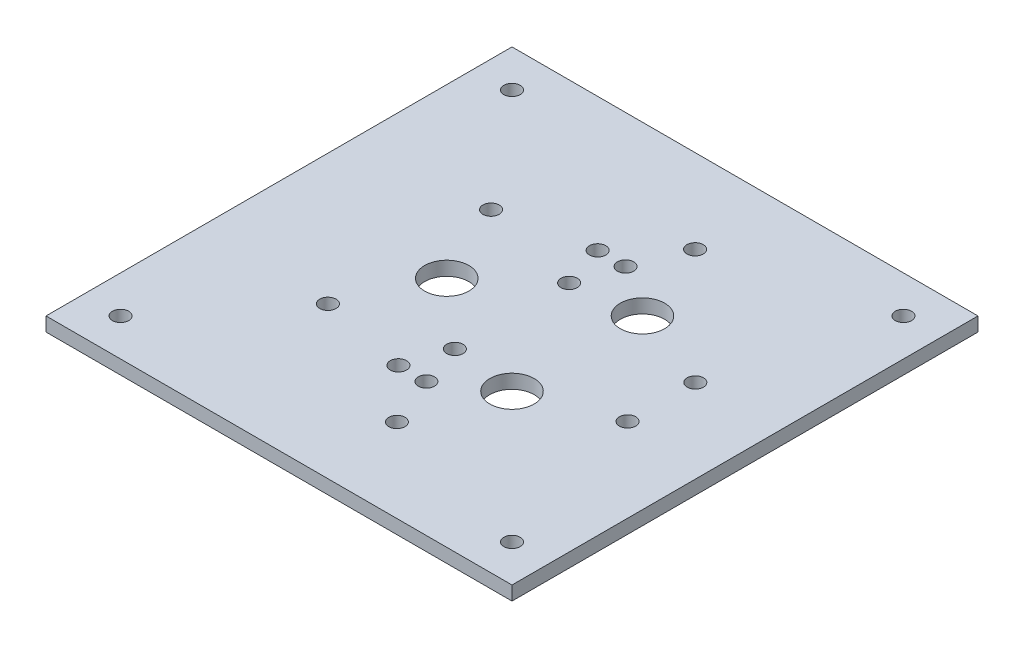
SolidWorks part; units mm, degrees
ref_plane "前视基准面" through (0, 0, 0) normal (0, 0, 1) x (1, 0, 0)
ref_plane "上视基准面" through (0, 0, 0) normal (0, 1, 0) x (1, 0, 0)
ref_plane "右视基准面" through (0, 0, 0) normal (1, 0, 0) x (0, 0, -1)
sketch "草图1" plane through (0, 0, 0) normal (0, 1, 0) x (1, 0, 0)
  arc B0 (6.5, 42.2787) -> (0, 49.247) centre (-4, 39) ccw
  circle B1 centre (10, 37.2645) radius 1.25
  line B2 (13.5, 42.2787) -> (13.5, 7.7213)
  line B3 (6.5, 7.7213) -> (6.5, 42.2787)
  line B4 (0, 50) -> (20, 50)
  circle B5 centre (13.5, 47.7547) radius 1.25
  circle B6 centre (6.5, 47.7547) radius 1.25
  circle B7 centre (10, 12.7355) radius 1.25
  arc B8 (0, 0.753) -> (6.5, 7.7213) centre (-4, 11) ccw
  circle B9 centre (6.5, 2.2453) radius 1.25
  circle B10 centre (13.5, 2.2453) radius 1.25
  line B11 (20, 0) -> (0, 0)
  arc B12 (20, 49.247) -> (13.5, 42.2787) centre (24, 39) ccw
  circle B13 centre (7, 3.6275) radius 1.25
  circle B14 centre (13, 3.6275) radius 1.25
  circle B15 centre (13, 46.3725) radius 1.25
  circle B16 centre (7, 46.3725) radius 1.25
sketch_block_instance "support_top-1"
sketch_block "support_top"
sketch_block_instance "support_top - 副本-1"
sketch_block "块2"
sketch "草图2" plane through (0, 0, 0) normal (0, 1, 0) x (1, 0, 0)
  line L0 (10, 75) -> (10, 50) construction
  line L1 (-40, 75) -> (60, 75)
  line L2 (-40, 75) -> (-40, -25)
  line L3 (-40, -25) -> (60, -25)
  line L4 (60, 75) -> (60, -25)
  line L5 (0, 50) -> (20, 50) construction
  line L6 (-40, 25) -> (6.5, 25) construction
  line L7 (6.5, 7.7213) -> (6.5, 42.2787) construction
  dimension "D1" = 100
  dimension "D2" = 100
extrude "凸台-拉伸1" add sketch "草图2" along normal blind 3
sketch "草图3" plane through (0, 3, 0) normal (0, 1, 0) x (1, 0, 0)
  circle A6 centre (13, 3.6275) radius 1.75
  circle A7 centre (7, 3.6275) radius 1.75
  circle A8 centre (10, 12.7355) radius 1.75
  circle A9 centre (13, 46.3725) radius 1.75
  circle A10 centre (7, 46.3725) radius 1.75
  circle A11 centre (10, 37.2645) radius 1.75
  dimension "D1" = 3.5
extrude "切除-拉伸1" cut sketch "草图3" against normal through all
sketch "草图6" plane through (0, 0, 0) normal (0, -1, 0) x (1, 0, 0)
  line L0 (-15, -25) -> (-40, -25)
  line L1 (-40, -75) -> (-40, 25) construction
  line L2 (10, 25) -> (10, 0)
  line L3 (-40, 25) -> (60, 25) construction
  line B0 (-15, -50) -> (-15, 0)
  circle B1 centre (17.5, -19) radius 1.25
  line B2 (35, 0) -> (35, -50)
  circle B3 centre (17.5, -31) radius 1.25
  circle B4 centre (-4, -25) radius 3.25
  circle B5 centre (24, -39) radius 3.25
  line B6 (35, -50) -> (-15, -50)
  circle B7 centre (29.5, -19) radius 1.25
  circle B8 centre (24, -11) radius 3.25
  line B9 (-15, 0) -> (35, 0)
sketch_block_instance "bottom-1"
sketch_block "块1"
sketch "草图7" plane through (0, 0, 0) normal (0, -1, 0) x (1, 0, 0)
  circle A0 centre (-4, -25) radius 3.25 construction
  circle A1 centre (24, -11) radius 3.25 construction
  circle A2 centre (24, -39) radius 3.25 construction
  line B0 (-8.5, -11.4446) -> (-8.5, -7.5)
  arc B1 (-15.5, -11.4446) -> (-15.5, -38.5554) centre (-12, -25) ccw
  arc B2 (-8.5, -38.5554) -> (-8.5, -11.4446) centre (-12, -25) ccw
  circle B3 centre (-4, -25) radius 4.5
  line B4 (-6, -26.5) -> (-2, -26.5)
  circle B5 centre (-12, -7.5) radius 2.1
  arc B6 (-2, -26.5) -> (-6, -26.5) centre (-4, -25) ccw
  circle B7 centre (-12, -42.5) radius 2.1
  arc B8 (-15.5, -42.5) -> (-8.5, -42.5) centre (-12, -42.5) ccw
  line B9 (-15.5, -7.5) -> (-15.5, -11.4446)
  line B10 (17.5846, -51.761) -> (14.7927, -54.5475)
  arc B11 (22.5296, -56.7155) -> (41.7183, -37.5635) centre (29.6514, -44.6623) ccw
  arc B12 (36.7732, -32.6091) -> (17.5846, -51.761) centre (29.6514, -44.6623) ccw
  circle B13 centre (24, -39) radius 4.5
  line B14 (26.4745, -39.3559) -> (23.6488, -36.5248)
  circle B15 centre (17.2652, -57.0248) radius 2.1
  arc B16 (23.6488, -36.5248) -> (26.4745, -39.3559) centre (24, -39) ccw
  circle B17 centre (42.0376, -32.2997) radius 2.1
  arc B18 (44.5101, -34.777) -> (39.5651, -29.8225) centre (42.0376, -32.2997) ccw
  arc B19 (14.7927, -54.5475) -> (19.7377, -59.502) centre (17.2652, -57.0248) ccw
  arc B20 (17.6499, 1.7936) -> (36.7404, -17.4562) centre (29.6803, -5.3667) ccw
  circle B21 centre (24, -11) radius 4.5
  line B22 (24.3638, -8.5266) -> (21.5237, -11.3433)
  circle B23 centre (42.0032, -17.7924) radius 2.1
  arc B24 (21.5237, -11.3433) -> (24.3638, -8.5266) centre (24, -11) ccw
  circle B25 centre (17.3575, 7.059) radius 2.1
  arc B26 (19.8426, 9.5235) -> (14.8723, 4.5944) centre (17.3575, 7.059) ccw
  line B27 (23.6362, -13.4734) -> (26.4763, -10.6567)
  line B28 (44.4883, -15.3278) -> (41.7107, -12.527)
  arc B29 (39.518, -20.2569) -> (44.4883, -15.3278) centre (42.0032, -17.7924) ccw
sketch_block_instance "stepperMotor-1"
sketch_block "stepperMotor"
sketch_block_instance "stepperMotor-5"
sketch_block_instance "stepperMotor-7"
sketch "草图8" plane through (0, 0, 0) normal (0, -1, 0) x (1, 0, 0)
  circle A0 centre (-4, -25) radius 4.75
  circle A1 centre (24, -11) radius 4.75
  circle A2 centre (24, -39) radius 4.75
  dimension "D1" = 9.5
extrude "切除-拉伸3" cut sketch "草图8" against normal through all
sketch "草图9" plane through (0, 0, 0) normal (0, -1, 0) x (-1, 0, 0)
  circle A0 centre (12, 7.5) radius 1.75
  circle A1 centre (-42.0032, 17.7924) radius 1.75
  circle A2 centre (-42.0376, 32.2997) radius 1.75
  circle A3 centre (12, 42.5) radius 1.75
  circle A4 centre (-17.2652, 57.0248) radius 1.75
  circle A5 centre (-17.3575, -7.059) radius 1.75
  dimension "D1" = 3.5
extrude "切除-拉伸4" cut sketch "草图9" against normal through all
sketch "草图10" plane through (0, 0, 0) normal (0, -1, 0) x (-1, 0, 0)
  line L0 (32, -17) -> (-52, -17) construction
  line L1 (-52, -17) -> (-52, 67) construction
  line L2 (-52, 67) -> (32, 67) construction
  line L3 (32, 67) -> (32, -17) construction
  line L4 (-10, -17) -> (-10, -25) construction
  line L5 (32, 25) -> (40, 25) construction
  line L6 (40, -25) -> (-60, -25) construction
  line L7 (40, 75) -> (40, -25) construction
  circle A0 centre (32, -17) radius 1.75
  circle A1 centre (32, 67) radius 1.75
  circle A2 centre (-52, 67) radius 1.75
  circle A3 centre (-52, -17) radius 1.75
  dimension "D1" = 3.5
  dimension "D2" = 8
  dimension "D3" = 8
extrude "切除-拉伸5" cut sketch "草图10" against normal blind 10
